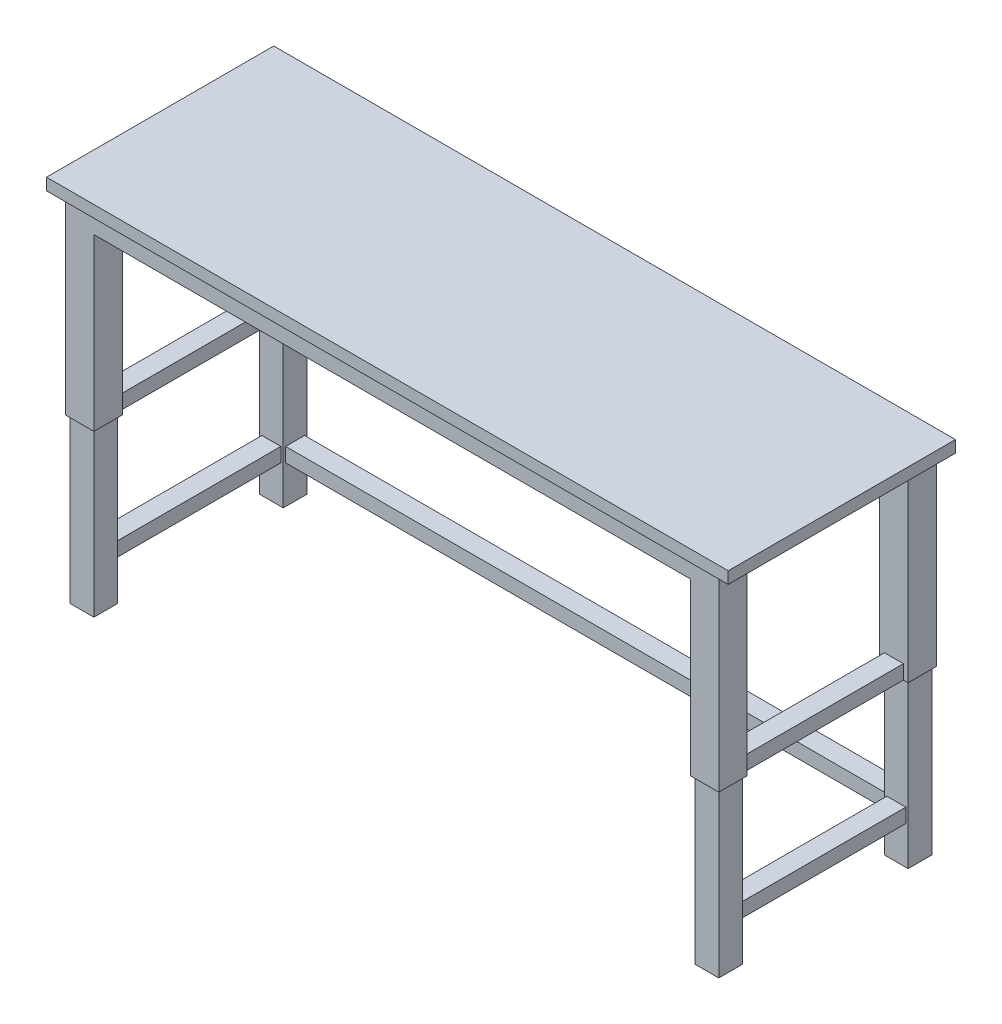
SolidWorks part; units mm, degrees
material "Plain Carbon Steel"
ref_plane "Front Plane" through (0, 0, 0) normal (0, 0, 1) x (1, 0, 0)
ref_plane "Top Plane" through (0, 0, 0) normal (0, 1, 0) x (1, 0, 0)
ref_plane "Right Plane" through (0, 0, 0) normal (1, 0, 0) x (0, 0, -1)
sketch "Sketch1" plane through (0, 0, 0) normal (0, 1, 0) x (1, 0, 0)
  line L1 (-914.4, -304.8) -> (914.4, -304.8)
  line L2 (-914.4, -304.8) -> (-914.4, 304.8)
  line L3 (-914.4, 304.8) -> (914.4, 304.8)
  line L4 (914.4, -304.8) -> (914.4, 304.8)
  line L5 (-914.4, -304.8) -> (914.4, 304.8) construction
  line L6 (-914.4, 304.8) -> (914.4, -304.8) construction
  point P0 (0, 0)
  dimension "D1" = 1828.8
  dimension "D2" = 609.6
extrude "Boss-Extrude1" add sketch "Sketch1" against normal blind 31.75
sketch "Sketch2" plane through (0, 0, 0) normal (1, 0, 0) x (0, 0, -1)
  line L0 (-304.8, -31.75) -> (304.8, -31.75) construction
  line L1 (-292.1, -31.75) -> (-215.9, -31.75)
  line L2 (-292.1, -31.75) -> (-292.1, -82.55)
  line L3 (-292.1, -82.55) -> (-215.9, -82.55)
  line L4 (-215.9, -31.75) -> (-215.9, -82.55)
  line L5 (215.9, -31.75) -> (292.1, -31.75)
  line L6 (215.9, -31.75) -> (215.9, -82.55)
  line L7 (215.9, -82.55) -> (292.1, -82.55)
  line L8 (292.1, -31.75) -> (292.1, -82.55)
  line L9 (-215.9, -31.75) -> (215.9, -31.75) construction
  line L10 (-304.8, -31.75) -> (-304.8, 0) construction
  point P10 (0, -31.75)
  dimension "D1" = 50.8
  dimension "D2" = 76.2
  dimension "D3" = 12.7
extrude "Boss-Extrude2" add sketch "Sketch2" along normal offset from surface 38.1 and the other way offset from surface 38.1 separate body up to face at (914.4, -15.875, 0) other way up to face at (-914.4, -15.875, 0)
sketch "Sketch3" plane through (0, -31.75, 0) normal (0, 1, 0) x (1, 0, 0)
  line L0 (876.3, -215.9) -> (-876.3, -215.9) construction
  line L1 (876.3, -292.1) -> (800.1, -292.1)
  line L2 (876.3, -292.1) -> (876.3, -215.9)
  line L3 (876.3, -215.9) -> (800.1, -215.9)
  line L4 (800.1, -292.1) -> (800.1, -215.9)
  line L5 (876.3, 215.9) -> (-876.3, 215.9) construction
  line L6 (-876.3, -292.1) -> (-800.1, -292.1)
  line L7 (-876.3, -292.1) -> (-876.3, -215.9)
  line L8 (-876.3, -215.9) -> (-800.1, -215.9)
  line L9 (-800.1, -292.1) -> (-800.1, -215.9)
  line L10 (-876.3, 292.1) -> (-800.1, 292.1)
  line L11 (-876.3, 292.1) -> (-876.3, 215.9)
  line L12 (-876.3, 215.9) -> (-800.1, 215.9)
  line L13 (-800.1, 292.1) -> (-800.1, 215.9)
  line L15 (876.3, 292.1) -> (800.1, 292.1)
  line L16 (876.3, 292.1) -> (876.3, 215.9)
  line L17 (876.3, 215.9) -> (800.1, 215.9)
  line L18 (800.1, 292.1) -> (800.1, 215.9)
extrude "Boss-Extrude3" add sketch "Sketch3" against normal blind 508
sketch "Sketch4" plane through (0, 0, 215.9) normal (0, 0, -1) x (-1, 0, 0)
  line L1 (-863.6, -501.65) -> (-812.8, -501.65)
  line L2 (-863.6, -501.65) -> (-863.6, -539.75)
  line L3 (-863.6, -539.75) -> (-812.8, -539.75)
  line L4 (-812.8, -501.65) -> (-812.8, -539.75)
  line L5 (800.1, -539.75) -> (876.3, -539.75) construction
  line L6 (812.8, -539.75) -> (863.6, -539.75)
  line L7 (812.8, -539.75) -> (812.8, -501.65)
  line L8 (812.8, -501.65) -> (863.6, -501.65)
  line L9 (863.6, -539.75) -> (863.6, -501.65)
  line L10 (-876.3, -539.75) -> (-800.1, -539.75) construction
  point P12 (-838.2, -539.75)
  point P13 (822.7477, -539.75)
  point P14 (838.2, -539.75)
  dimension "D1" = 50.8
  dimension "D2" = 38.1
extrude "Boss-Extrude4" add sketch "Sketch4" along normal up to surface (431.8 mm away) up to face at (0, -298.45, -215.9)
ref_plane "Plane1" through (0, -977.9, 0) normal (0, 1, 0) x (1, 0, 0)
sketch "Sketch6" plane through (0, -977.9, 0) normal (0, 1, 0) x (1, 0, 0)
  line L0 (-806.45, 285.75) -> (-869.95, 285.75)
  line L1 (-869.95, 285.75) -> (-869.95, 222.25)
  line L2 (-869.95, 222.25) -> (-806.45, 222.25)
  line L3 (-806.45, 222.25) -> (-806.45, 285.75)
  line L4 (-800.1, 292.1) -> (-876.3, 292.1)
  line L5 (-800.1, 215.9) -> (-800.1, 292.1)
  line L6 (-876.3, 215.9) -> (-800.1, 215.9)
  line L7 (-876.3, 292.1) -> (-876.3, 215.9)
  line L8 (-800.1, 292.1) -> (-876.3, 292.1) construction
  line L9 (-800.1, 215.9) -> (-800.1, 292.1) construction
  line L10 (-876.3, 215.9) -> (-800.1, 215.9) construction
  line L11 (-876.3, 292.1) -> (-876.3, 215.9) construction
  line L12 (-876.3, -292.1) -> (-800.1, -292.1)
  line L13 (-800.1, -292.1) -> (-800.1, -215.9)
  line L14 (-800.1, -215.9) -> (-876.3, -215.9)
  line L15 (-876.3, -215.9) -> (-876.3, -292.1)
  line L16 (-876.3, -292.1) -> (-800.1, -292.1) construction
  line L17 (-800.1, -292.1) -> (-800.1, -215.9) construction
  line L18 (-800.1, -215.9) -> (-876.3, -215.9) construction
  line L19 (-876.3, -215.9) -> (-876.3, -292.1) construction
  line L20 (800.1, -292.1) -> (876.3, -292.1)
  line L21 (800.1, -215.9) -> (800.1, -292.1)
  line L22 (876.3, -215.9) -> (800.1, -215.9)
  line L23 (876.3, -292.1) -> (876.3, -215.9)
  line L24 (800.1, -292.1) -> (876.3, -292.1) construction
  line L25 (800.1, -215.9) -> (800.1, -292.1) construction
  line L26 (876.3, -215.9) -> (800.1, -215.9) construction
  line L27 (876.3, -292.1) -> (876.3, -215.9) construction
  line L28 (876.3, 292.1) -> (800.1, 292.1)
  line L29 (800.1, 292.1) -> (800.1, 215.9)
  line L30 (800.1, 215.9) -> (876.3, 215.9)
  line L31 (876.3, 215.9) -> (876.3, 292.1)
  line L32 (876.3, 292.1) -> (800.1, 292.1) construction
  line L33 (800.1, 292.1) -> (800.1, 215.9) construction
  line L34 (800.1, 215.9) -> (876.3, 215.9) construction
  line L35 (876.3, 215.9) -> (876.3, 292.1) construction
  line L36 (-869.95, -285.75) -> (-806.45, -285.75)
  line L37 (-806.45, -285.75) -> (-806.45, -222.25)
  line L38 (-806.45, -222.25) -> (-869.95, -222.25)
  line L39 (-869.95, -222.25) -> (-869.95, -285.75)
  line L40 (806.45, -285.75) -> (869.95, -285.75)
  line L41 (869.95, -285.75) -> (869.95, -222.25)
  line L42 (869.95, -222.25) -> (806.45, -222.25)
  line L43 (806.45, -222.25) -> (806.45, -285.75)
  line L44 (869.95, 285.75) -> (806.45, 285.75)
  line L45 (806.45, 285.75) -> (806.45, 222.25)
  line L46 (806.45, 222.25) -> (869.95, 222.25)
  line L47 (869.95, 222.25) -> (869.95, 285.75)
  dimension "D5" = 63.5
  dimension "D1" = 0
  dimension "D2" = 0
  dimension "D3" = 0
  dimension "D4" = 0
extrude "Boss-Extrude5" add sketch "Sketch6" along normal up to surface (438.15 mm away) separate body up to face at (838.2, -539.75, 0)
sketch "Sketch7" plane through (0, 0, 222.25) normal (0, 0, -1) x (-1, 0, 0)
  line L1 (-863.6, -876.3) -> (-812.8, -876.3)
  line L2 (-863.6, -876.3) -> (-863.6, -838.2)
  line L3 (-863.6, -838.2) -> (-812.8, -838.2)
  line L4 (-812.8, -876.3) -> (-812.8, -838.2)
  line L5 (812.8, -876.3) -> (863.6, -876.3)
  line L6 (812.8, -876.3) -> (812.8, -838.2)
  line L7 (812.8, -838.2) -> (863.6, -838.2)
  line L8 (863.6, -876.3) -> (863.6, -838.2)
  line L9 (-863.6, -501.65) -> (-863.6, -539.75) construction
  line L10 (863.6, -539.75) -> (863.6, -501.65) construction
  line L14 (-812.8, -501.65) -> (-863.6, -501.65) construction
  line L15 (-869.95, -977.9) -> (-806.45, -977.9) construction
  point P14 (-796.3147, -857.9908)
  point P15 (0, 0)
  dimension "D1" = 101.6
extrude "Boss-Extrude6" add sketch "Sketch7" along normal up to surface (444.5 mm away) up to face at (838.2, -758.825, -222.25)
sketch "Sketch8" plane through (806.45, 0, 0) normal (-1, 0, 0) x (0, 0, 1)
  line L0 (-222.25, -876.3) -> (-222.25, -838.2) construction
  line L1 (-279.4, -876.3) -> (-228.6, -876.3)
  line L2 (-279.4, -876.3) -> (-279.4, -838.2)
  line L3 (-279.4, -838.2) -> (-228.6, -838.2)
  line L4 (-228.6, -876.3) -> (-228.6, -838.2)
  line L5 (-222.25, -876.3) -> (222.25, -876.3) construction
  line L6 (-285.75, -977.9) -> (-222.25, -977.9) construction
  point P10 (-254, -977.9)
  point P11 (-254, -876.3)
  dimension "D1" = 50.8
extrude "Boss-Extrude7" add sketch "Sketch8" along normal up to surface (1612.9 mm away) up to face at (-806.45, -758.825, -254)
